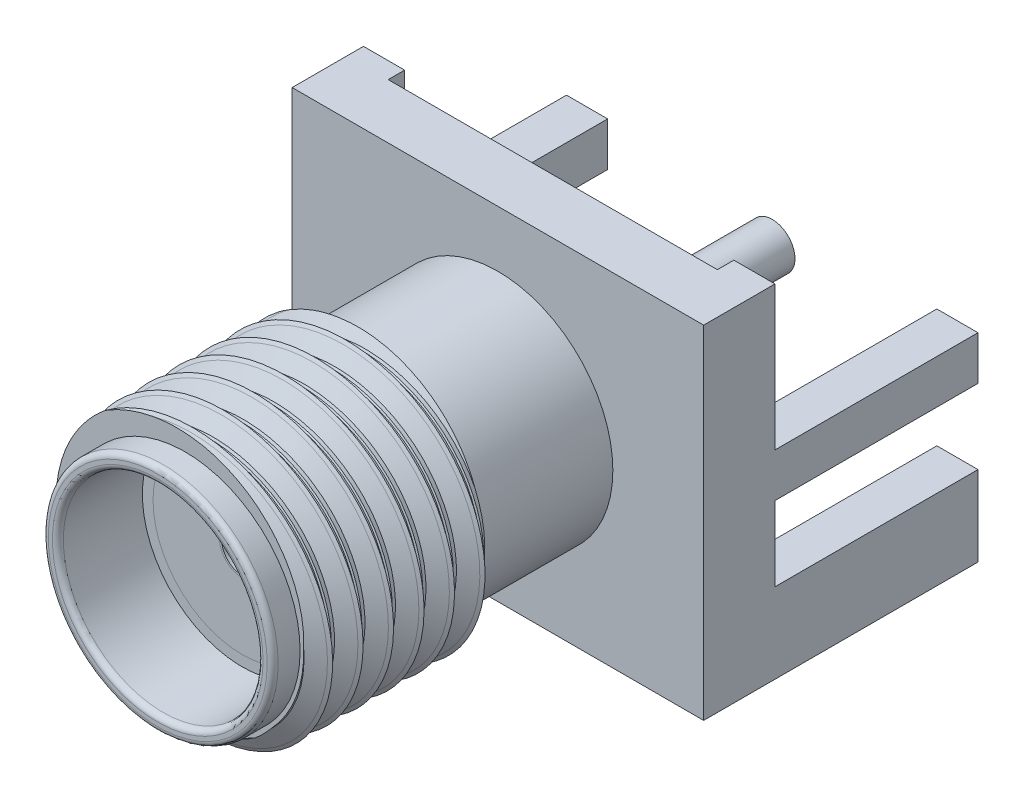
SolidWorks part; units mm, degrees
material "Brass"
ref_plane "Front Plane" through (0, 0, 0) normal (0, 0, 1) x (1, 0, 0)
ref_plane "Top Plane" through (0, 0, 0) normal (0, 1, 0) x (1, 0, 0)
ref_plane "Right Plane" through (0, 0, 0) normal (1, 0, 0) x (0, 0, -1)
sketch "Sketch1" plane through (0, 0, 0) normal (0, 0, 1) x (1, 0, 0)
  circle A0 centre (0, 0) radius 2.6607
  dimension "D1" = 5.3213
extrude "Boss-Extrude1" add sketch "Sketch1" along normal blind 7.874
sketch "Sketch2" plane through (0, 0, 7.874) normal (0, 0, 1) x (1, 0, 0)
  circle A0 centre (0, 0) radius 2.3114
  dimension "D1" = 4.6228
extrude "Cut-Extrude1" cut sketch "Sketch2" against normal blind 1.9558
sketch "Sketch5" plane through (0, 0, 0) normal (0, 0, -1) x (-1, 0, 0)
  line L0 (0, 2.6607) -> (0, 3.9624) construction
  line L1 (-4.7625, 3.9624) -> (4.7625, 3.9624)
  line L2 (-4.7625, 3.9624) -> (-4.7625, -3.9624)
  line L3 (-4.7625, -3.9624) -> (4.7625, -3.9624)
  line L4 (4.7625, 3.9624) -> (4.7625, -3.9624)
  line L5 (2.6607, 0) -> (4.7625, 0) construction
  circle A0 centre (0, 0) radius 2.6607 construction
  circle A1 centre (0, 0) radius 2.6607 construction
  circle A2 centre (0, 0) radius 2.032
  dimension "D3" = 4.064
  dimension "D1" = 9.525
  dimension "D2" = 7.9248
extrude "Boss-Extrude2" add sketch "Sketch5" along normal blind 1.651 separate body
sketch "Sketch6" plane through (0, 3.9624, 0) normal (0, 1, 0) x (1, 0, 0)
  line L0 (-4.7625, 1.651) -> (4.7625, 1.651) construction
  line L1 (-3.81, 1.651) -> (3.81, 1.651)
  line L2 (-3.81, 1.651) -> (-3.81, 1.27)
  line L3 (-3.81, 1.27) -> (3.81, 1.27)
  line L4 (3.81, 1.651) -> (3.81, 1.27)
  line L5 (-4.7625, 0) -> (4.7625, 0) construction
  line L6 (0, 1.27) -> (0, 0) construction
  dimension "D1" = 1.27
  dimension "D2" = 7.62
extrude "Cut-Extrude2" cut sketch "Sketch6" against normal through all
sketch "Sketch7" plane through (0, 0, 5.9182) normal (0, 0, 1) x (1, 0, 0)
  circle A0 centre (0, 0) radius 0.4763
  dimension "D1" = 0.9525
extrude "Cut-Extrude3" cut sketch "Sketch7" against normal through all
sketch "Sketch8" plane through (0, 0, 5.9182) normal (0, 0, 1) x (1, 0, 0)
  circle A0 centre (0, 0) radius 2.0638
  circle A4 centre (0, 0) radius 0.5259
  circle A5 centre (0, 0) radius 0.5259
  dimension "D1" = 4.1275
  dimension "D2" = 0.0496
split line "Split Line1"
sketch "Sketch9" plane through (0, 0, 0) normal (0, 0, 1) x (1, 0, 0)
  circle A0 centre (0, 0) radius 0.5259 construction
  circle A1 centre (0, 0) radius 0.5259
extrude "Boss-Extrude4" add sketch "Sketch9" against normal offset from surface (6.35 mm away) 5.08 separate body up to face at (2.032, 0, -1.27) offset beyond the face yes
sketch "Sketch10" plane through (0, 0, -1.651) normal (0, 0, -1) x (-1, 0, 0)
  line L0 (3.81, -3.9624) -> (3.81, 3.9624) construction
  line L1 (3.81, 0.635) -> (4.7625, 0.635)
  line L2 (3.81, 0.635) -> (3.81, -0.381)
  line L3 (3.81, -0.381) -> (4.7625, -0.381)
  line L4 (4.7625, 0.635) -> (4.7625, -0.381)
  line L5 (4.7625, -3.9624) -> (4.7625, 3.9624) construction
  line L7 (3.81, -2.1082) -> (4.7625, -2.1082)
  line L8 (3.81, -2.1082) -> (3.81, -3.9624)
  line L9 (3.81, -3.9624) -> (4.7625, -3.9624)
  line L10 (4.7625, -2.1082) -> (4.7625, -3.9624)
  line L11 (3.81, -3.9624) -> (4.7625, -3.9624) construction
  line L12 (0, -1000) -> (0, 49000) construction
  line L13 (-4.7625, -2.1082) -> (-4.7625, -3.9624)
  line L14 (-3.81, -3.9624) -> (-4.7625, -3.9624)
  line L15 (-3.81, -2.1082) -> (-3.81, -3.9624)
  line L16 (-3.81, -2.1082) -> (-4.7625, -2.1082)
  line L17 (-4.7625, 0.635) -> (-4.7625, -0.381)
  line L18 (-3.81, -0.381) -> (-4.7625, -0.381)
  line L19 (-3.81, 0.635) -> (-3.81, -0.381)
  line L20 (-3.81, 0.635) -> (-4.7625, 0.635)
  dimension "D1" = 1.016
  dimension "D2" = 1.7272
  dimension "D3" = 1.8542
extrude "Boss-Extrude5" add sketch "Sketch10" along normal up to surface (4.699 mm away) up to face at (0.5259, 0, -6.35)
sketch "Sketch12" plane through (0, 0, 7.874) normal (0, 0, 1) x (1, 0, 0)
  circle A1 centre (0, 0) radius 3.1636
  dimension "MajorDiameter" = 6.3271
sketch "Sketch13" plane through (0, 0, 7.874) normal (0, 0, 1) x (1, 0, 0)
  circle A0 centre (0, 0) radius 3.1636
  circle A1 centre (0, 0) radius 2.6607
  circle A2 centre (0, 0) radius 2.6607 construction
extrude "Boss-Extrude6" add sketch "Sketch13" against normal blind 4.191 from offset 0.635
curve "Helix/Spiral1" pitch 0.7056 height 7.0556 turns 10 parameters "Pitch"=0.7056
sketch "Sketch15" plane through (0, 0, 0) normal (1, 0, 0) x (0, 0, -1)
  line L0 (-7.874, 3.1636) -> (-7.874, -3.1636) construction
  line L1 (-6.4629, 3.1636) -> (-7.1684, 3.1636) construction
  line L2 (-7.1684, 3.1636) -> (-7.874, 3.1636) construction
  line L3 (-10.4133, 2.7445) -> (0, 2.7445) construction
  line L4 (-10.4133, 2.7445) -> (-10.4133, -2.7445) construction
  line L5 (-7.874, 0) -> (-10.4133, 0) construction
  line L6 (0, 3.9624) -> (0, -3.9624) construction
  line L7 (-6.4629, 3.1636) -> (-5.7573, 3.1636) construction
  line L8 (-8.4915, 3.0883) -> (-8.4033, 3.0883) construction
  line L9 (-8.4033, 3.0883) -> (-8.2048, 2.7445)
  line L10 (-8.2048, 2.7445) -> (-8.1166, 2.7445)
  line L11 (-7.874, 2.6607) -> (-7.874, -2.6607) construction
  line L12 (-3.048, 3.1636) -> (-7.239, 3.1636) construction
  line L13 (-8.1166, 2.7445) -> (-7.9181, 3.0883)
  line L14 (-7.9181, 3.0883) -> (-7.8299, 3.0883) construction
  line L15 (-7.8299, 3.0883) -> (-7.6314, 2.7445)
  line L16 (-7.6314, 2.7445) -> (-7.5432, 2.7445)
  line L17 (-7.5432, 2.7445) -> (-7.3447, 3.0883)
  line L18 (-7.3447, 3.0883) -> (-7.2565, 3.0883) construction
  line L19 (-8.1607, 2.7445) -> (-8.1607, 3.9348) construction
  line L20 (-7.9181, 3.0883) -> (-8.4033, 3.0883) construction
  line L21 (-7.5873, 2.7445) -> (-7.5873, 3.9348) construction
  line L22 (-7.3447, 3.0883) -> (-7.8299, 3.0883) construction
  line L23 (-7.874, 3.1636) -> (-7.874, 3.9348) construction
  line L24 (-7.9181, 3.0883) -> (-7.874, 3.1636)
  line L25 (-7.874, 3.1636) -> (-7.8299, 3.0883)
  line L26 (-7.3447, 3.0883) -> (-7.3447, 4.147)
  line L27 (-7.3447, 4.147) -> (-8.4033, 4.147)
  line L28 (-8.4033, 4.147) -> (-8.4033, 3.0883)
  spline S0 degree 3 poles (30.3197, -1996.2874) (-9.6986, -238.0579) (-8.6725, 16.4609) (-7.7858, 2.2952) (-7.7417, 1.2422) (-7.6976, 0) (-7.6535, -1.2422) (-7.6094, -2.2952) (-7.5653, -2.9988) (-7.5212, -3.2459) (-7.4771, -2.9988) (-7.433, -2.2952) (-7.3889, -1.2422) (-7.3448, 0) (-7.3007, 1.2422) (-7.2566, 2.2952) (-7.2125, 2.9988) (-7.1684, 3.2459) (-7.1243, 2.9988) (-7.0803, 2.2952) (-7.0362, 1.2422) (-6.9921, 0) (-6.948, -1.2422) (-6.9039, -2.2952) (-6.8598, -2.9988) (-6.8157, -3.2459) (-6.7716, -2.9988) (-6.7275, -2.2952) (-6.6834, -1.2422) (-6.6393, 0) (-6.5952, 1.2422) (-6.5511, 2.2952) (-6.507, 2.9988) (-6.4629, 3.2459) (-6.4188, 2.9988) (-6.3747, 2.2952) (-6.3306, 1.2422) (-6.2865, 0) (-6.2424, -1.2422) (-6.1983, -2.2952) (-6.1542, -2.9988) (-6.1101, -3.2459) (-6.066, -2.9988) (-6.0219, -2.2952) (-5.9778, -1.2422) (-5.9337, 0) (-5.8896, 1.2422) (-5.8455, 2.2952) (-5.8014, 2.9988) (-5.7573, 3.2459) (-5.7132, 2.9988) (-5.6691, 2.2952) (-5.625, 1.2422) (-5.5809, 0) (-5.5368, -1.2422) (-5.4927, -2.2952) (-5.4487, -2.9988) (-5.4046, -3.2459) (-5.3605, -2.9988) (-5.3164, -2.2952) (-5.2723, -1.2422) (-5.2282, 0) (-5.1841, 1.2422) (-5.14, 2.2952) (-5.0959, 2.9988) (-5.0518, 3.2459) (-5.0077, 2.9988) (-4.9636, 2.2952) (-4.9195, 1.2422) (-4.8754, 0) (-4.8313, -1.2422) (-4.7872, -2.2952) (-4.7431, -2.9988) (-4.699, -3.2459) (-4.6549, -2.9988) (-4.6108, -2.2952) (-4.5667, -1.2422) (-4.5226, 0) (-4.4785, 1.2422) (-4.4344, 2.2952) (-4.3903, 2.9988) (-4.3462, 3.2459) (-4.3021, 2.9988) (-4.258, 2.2952) (-4.2139, 1.2422) (-4.1698, 0) (-4.1257, -1.2422) (-4.0816, -2.2952) (-4.0375, -2.9988) (-3.9934, -3.2459) (-3.9493, -2.9988) (-3.9052, -2.2952) (-3.8612, -1.2422) (-3.8171, 0) (-3.773, 1.2422) (-3.7289, 2.2952) (-3.6848, 2.9988) (-3.6407, 3.2459) (-3.5966, 2.9988) (-3.5525, 2.2952) (-3.5084, 1.2422) (-3.4643, 0) (-3.4202, -1.2422) (-3.3761, -2.2952) (-3.332, -2.9988) (-3.2879, -3.2459) (-3.2438, -2.9988) (-3.1997, -2.2952) (-3.1556, -1.2422) (-3.1115, 0) (-3.0674, 1.2422) (-3.0233, 2.2952) (-2.9792, 2.9988) (-2.9351, 3.2459) (-2.891, 2.9988) (-2.8469, 2.2952) (-2.8028, 1.2422) (-2.7587, 0) (-2.7146, -1.2422) (-2.6705, -2.2952) (-2.6264, -2.9988) (-2.5823, -3.2459) (-2.5382, -2.9988) (-2.4941, -2.2952) (-2.45, -1.2422) (-2.4059, 0) (-2.3618, 1.2422) (-2.3177, 2.2952) (-2.2737, 2.9988) (-2.2296, 3.2459) (-2.1855, 2.9988) (-2.1414, 2.2952) (-2.0973, 1.2422) (-2.0532, 0) (-2.0091, -1.2422) (-1.965, -2.2952) (-1.9209, -2.9988) (-1.8768, -3.2459) (-1.8327, -2.9988) (-1.7886, -2.2952) (-1.7445, -1.2422) (-1.7004, 0) (-1.6563, 1.2422) (-1.6122, 2.2952) (-1.5681, 2.9988) (-1.524, 3.2459) (-1.4799, 2.9988) (-1.4358, 2.2952) (-1.3917, 1.2422) (-1.3476, 0) (-1.3035, -1.2422) (-1.2594, -2.2952) (-1.2153, -2.9988) (-1.1712, -3.2459) (-1.1271, -2.9988) (-1.083, -2.2952) (-1.0389, -1.2422) (-0.9948, 0) (-0.9507, 1.2422) (-0.9066, 2.2952) (-0.02, 16.461) (1.0062, -238.0612) (-39.0129, -1996.3232) knots -0.358731 -0.358731 -0.358731 -0.358731 0.00625 0.0125 0.01875 0.025 0.03125 0.0375 0.04375 0.05 0.05625 0.0625 0.06875 0.075 0.08125 0.0875 0.09375 0.1 0.10625 0.1125 0.11875 0.125 0.13125 0.1375 0.14375 0.15 0.15625 0.1625 0.16875 0.175 0.18125 0.1875 0.19375 0.2 0.20625 0.2125 0.21875 0.225 0.23125 0.2375 0.24375 0.25 0.25625 0.2625 0.26875 0.275 0.28125 0.2875 0.29375 0.3 0.30625 0.3125 0.31875 0.325 0.33125 0.3375 0.34375 0.35 0.35625 0.3625 0.36875 0.375 0.38125 0.3875 0.39375 0.4 0.40625 0.4125 0.41875 0.425 0.43125 0.4375 0.44375 0.45 0.45625 0.4625 0.46875 0.475 0.48125 0.4875 0.49375 0.5 0.50625 0.5125 0.51875 0.525 0.53125 0.5375 0.54375 0.55 0.55625 0.5625 0.56875 0.575 0.58125 0.5875 0.59375 0.6 0.60625 0.6125 0.61875 0.625 0.63125 0.6375 0.64375 0.65 0.65625 0.6625 0.66875 0.675 0.68125 0.6875 0.69375 0.7 0.70625 0.7125 0.71875 0.725 0.73125 0.7375 0.74375 0.75 0.75625 0.7625 0.76875 0.775 0.78125 0.7875 0.79375 0.8 0.80625 0.8125 0.81875 0.825 0.83125 0.8375 0.84375 0.85 0.85625 0.8625 0.86875 0.875 0.88125 0.8875 0.89375 0.9 0.90625 0.9125 0.91875 0.925 0.93125 0.9375 0.94375 0.95 0.95625 0.9625 0.96875 0.975 0.98125 0.9875 0.99375 1.358734 1.358734 1.358734 1.358734 only from (-7.874, 3.1636) to (-0.8184, 3.1636) construction
  spline S1 degree 3 poles (-7.874, 3.1636) (-7.8594, 3.1636) (-7.8299, 2.9988) (-7.7858, 2.2952) (-7.7417, 1.2422) (-7.6976, 0) (-7.6535, -1.2422) (-7.6094, -2.2952) (-7.5653, -2.9988) (-7.5212, -3.2459) (-7.4771, -2.9988) (-7.433, -2.2952) (-7.3889, -1.2422) (-7.3448, 0) (-7.3007, 1.2422) (-7.2566, 2.2952) (-7.2125, 2.9988) (-7.1684, 3.2459) (-7.1243, 2.9988) (-7.0803, 2.2952) (-7.0362, 1.2422) (-6.9921, 0) (-6.948, -1.2422) (-6.9039, -2.2952) (-6.8598, -2.9988) (-6.8157, -3.2459) (-6.7716, -2.9988) (-6.7275, -2.2952) (-6.6834, -1.2422) (-6.6393, 0) (-6.5952, 1.2422) (-6.5511, 2.2952) (-6.507, 2.9988) (-6.4629, 3.2459) (-6.4188, 2.9988) (-6.3747, 2.2952) (-6.3306, 1.2422) (-6.2865, 0) (-6.2424, -1.2422) (-6.1983, -2.2952) (-6.1542, -2.9988) (-6.1101, -3.2459) (-6.066, -2.9988) (-6.0219, -2.2952) (-5.9778, -1.2422) (-5.9337, 0) (-5.8896, 1.2422) (-5.8455, 2.2952) (-5.8014, 2.9988) (-5.7573, 3.2459) (-5.7132, 2.9988) (-5.6691, 2.2952) (-5.625, 1.2422) (-5.5809, 0) (-5.5368, -1.2422) (-5.4927, -2.2952) (-5.4487, -2.9988) (-5.4046, -3.2459) (-5.3605, -2.9988) (-5.3164, -2.2952) (-5.2723, -1.2422) (-5.2282, 0) (-5.1841, 1.2422) (-5.14, 2.2952) (-5.0959, 2.9988) (-5.0518, 3.2459) (-5.0077, 2.9988) (-4.9636, 2.2952) (-4.9195, 1.2422) (-4.8754, 0) (-4.8313, -1.2422) (-4.7872, -2.2952) (-4.7431, -2.9988) (-4.699, -3.2459) (-4.6549, -2.9988) (-4.6108, -2.2952) (-4.5667, -1.2422) (-4.5226, 0) (-4.4785, 1.2422) (-4.4344, 2.2952) (-4.3903, 2.9988) (-4.3462, 3.2459) (-4.3021, 2.9988) (-4.258, 2.2952) (-4.2139, 1.2422) (-4.1698, 0) (-4.1257, -1.2422) (-4.0816, -2.2952) (-4.0375, -2.9988) (-3.9934, -3.2459) (-3.9493, -2.9988) (-3.9052, -2.2952) (-3.8612, -1.2422) (-3.8171, 0) (-3.773, 1.2422) (-3.7289, 2.2952) (-3.6848, 2.9988) (-3.6407, 3.2459) (-3.5966, 2.9988) (-3.5525, 2.2952) (-3.5084, 1.2422) (-3.4643, 0) (-3.4202, -1.2422) (-3.3761, -2.2952) (-3.332, -2.9988) (-3.2879, -3.2459) (-3.2438, -2.9988) (-3.1997, -2.2952) (-3.1556, -1.2422) (-3.1115, 0) (-3.0674, 1.2422) (-3.0233, 2.2952) (-2.9792, 2.9988) (-2.9351, 3.2459) (-2.891, 2.9988) (-2.8469, 2.2952) (-2.8028, 1.2422) (-2.7587, 0) (-2.7146, -1.2422) (-2.6705, -2.2952) (-2.6264, -2.9988) (-2.5823, -3.2459) (-2.5382, -2.9988) (-2.4941, -2.2952) (-2.45, -1.2422) (-2.4059, 0) (-2.3618, 1.2422) (-2.3177, 2.2952) (-2.2737, 2.9988) (-2.2296, 3.2459) (-2.1855, 2.9988) (-2.1414, 2.2952) (-2.0973, 1.2422) (-2.0532, 0) (-2.0091, -1.2422) (-1.965, -2.2952) (-1.9209, -2.9988) (-1.8768, -3.2459) (-1.8327, -2.9988) (-1.7886, -2.2952) (-1.7445, -1.2422) (-1.7004, 0) (-1.6563, 1.2422) (-1.6122, 2.2952) (-1.5681, 2.9988) (-1.524, 3.2459) (-1.4799, 2.9988) (-1.4358, 2.2952) (-1.3917, 1.2422) (-1.3476, 0) (-1.3035, -1.2422) (-1.2594, -2.2952) (-1.2153, -2.9988) (-1.1712, -3.2459) (-1.1271, -2.9988) (-1.083, -2.2952) (-1.0389, -1.2422) (-0.9948, 0) (-0.9507, 1.2422) (-0.9066, 2.2952) (-0.8626, 2.9988) (-0.833, 3.1636) (-0.8184, 3.1636) knots 0 0 0 0 0.00625 0.0125 0.01875 0.025 0.03125 0.0375 0.04375 0.05 0.05625 0.0625 0.06875 0.075 0.08125 0.0875 0.09375 0.1 0.10625 0.1125 0.11875 0.125 0.13125 0.1375 0.14375 0.15 0.15625 0.1625 0.16875 0.175 0.18125 0.1875 0.19375 0.2 0.20625 0.2125 0.21875 0.225 0.23125 0.2375 0.24375 0.25 0.25625 0.2625 0.26875 0.275 0.28125 0.2875 0.29375 0.3 0.30625 0.3125 0.31875 0.325 0.33125 0.3375 0.34375 0.35 0.35625 0.3625 0.36875 0.375 0.38125 0.3875 0.39375 0.4 0.40625 0.4125 0.41875 0.425 0.43125 0.4375 0.44375 0.45 0.45625 0.4625 0.46875 0.475 0.48125 0.4875 0.49375 0.5 0.50625 0.5125 0.51875 0.525 0.53125 0.5375 0.54375 0.55 0.55625 0.5625 0.56875 0.575 0.58125 0.5875 0.59375 0.6 0.60625 0.6125 0.61875 0.625 0.63125 0.6375 0.64375 0.65 0.65625 0.6625 0.66875 0.675 0.68125 0.6875 0.69375 0.7 0.70625 0.7125 0.71875 0.725 0.73125 0.7375 0.74375 0.75 0.75625 0.7625 0.76875 0.775 0.78125 0.7875 0.79375 0.8 0.80625 0.8125 0.81875 0.825 0.83125 0.8375 0.84375 0.85 0.85625 0.8625 0.86875 0.875 0.88125 0.8875 0.89375 0.9 0.90625 0.9125 0.91875 0.925 0.93125 0.9375 0.94375 0.95 0.95625 0.9625 0.96875 0.975 0.98125 0.9875 0.99375 1 1 1 1 construction
  point P29 (-8.1607, 3.0883)
  point P32 (-7.5873, 3.0883)
  point P33 (-7.874, 3.0883)
  dimension "D1" = 60
  dimension "MinorDiameter" = 5.4889
  dimension "D2" = 0.5734
  dimension "8thPitch" = 0.0882
sweep "Cut-Sweep5" cut profiles "Sketch15" path "Helix/Spiral1"
fillet "Fillet1" radius 0.127 2 edges at (2.3114, 0, 7.874) (2.6607, 0, 7.874)
equation "\"MajorDiameter\"= 0.2491"
equation "\"MinorDiameter\"= 0.2161"
equation "\"Theta\"= 60"
equation "\"Pitch\"= 1/36 "
equation "\"8thPitch\"= \"Pitch\"/8"
